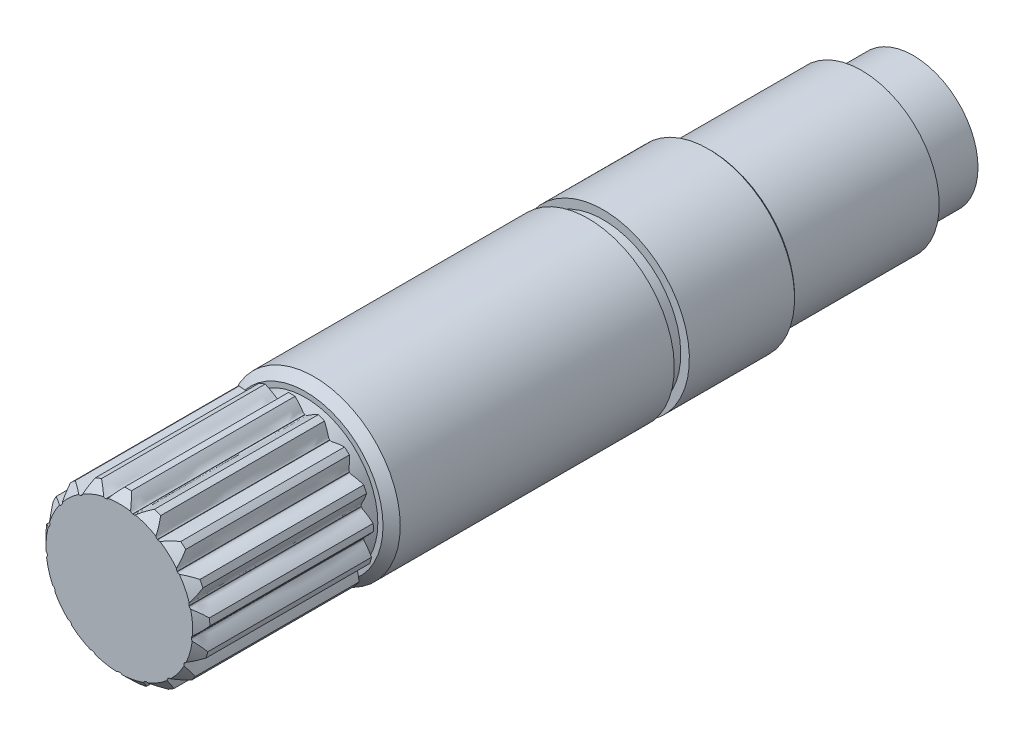
SolidWorks part; units mm, degrees
material "Alloy Steel"
ref_plane "Front Plane" through (0, 0, 0) normal (0, 0, 1) x (1, 0, 0)
ref_plane "Top Plane" through (0, 0, 0) normal (0, 1, 0) x (1, 0, 0)
ref_plane "Right Plane" through (0, 0, 0) normal (1, 0, 0) x (0, 0, -1)
sketch "Sketch12" plane through (0, 0, 0) normal (0, 0, 1) x (1, 0, 0)
  circle A0 centre (0, 0) radius 10
  dimension "D1" = 20
extrude "Shaft" add sketch "Sketch12" along normal mid plane 43
sketch "Sketch13" plane through (0, 0, 21.5) normal (0, 0, 1) x (1, 0, 0)
  circle A0 centre (0, 0) radius 8.3981
  dimension "D1" = 16.7963
extrude "Motor side relief" add sketch "Sketch13" along normal blind 1.587
sketch "Sketch14" plane through (0, 0, -21.5) normal (0, 0, -1) x (-1, 0, 0)
  circle A0 centre (0, 0) radius 8.3981
  dimension "D1" = 16.7963
sketch "Sketch15" plane through (0, 0, 23.087) normal (0, 0, 1) x (1, 0, 0)
  line L38 (4.4402, 7.1283) -> (4.4211, 7.1402)
  line L39 (4.4211, 7.1402) -> (4.4019, 7.1521)
  line L40 (1.5653, 8.251) -> (1.5432, 8.2552)
  line L41 (1.5432, 8.2552) -> (1.521, 8.2593)
  line L42 (-1.521, 8.2593) -> (-1.5432, 8.2552)
  line L43 (-1.5432, 8.2552) -> (-1.5653, 8.251)
  line L44 (-4.4019, 7.1521) -> (-4.4211, 7.1402)
  line L45 (-4.4211, 7.1402) -> (-4.4402, 7.1283)
  line L46 (-6.6882, 5.079) -> (-6.7019, 5.061)
  line L47 (-6.7019, 5.061) -> (-6.7154, 5.043)
  line L48 (-8.0713, 2.32) -> (-8.0776, 2.2983)
  line L49 (-8.0776, 2.2983) -> (-8.0837, 2.2766)
  line L50 (-8.3644, -0.7524) -> (-8.3623, -0.7749)
  line L51 (-8.3623, -0.7749) -> (-8.3602, -0.7973)
  line L52 (-7.5277, -3.7232) -> (-7.5177, -3.7434)
  line L53 (-7.5177, -3.7434) -> (-7.5076, -3.7636)
  line L54 (-5.6744, -6.1911) -> (-5.6578, -6.2063)
  line L55 (-5.6578, -6.2063) -> (-5.6411, -6.2215)
  line L56 (-3.0548, -7.8229) -> (-3.0338, -7.831)
  line L57 (-3.0338, -7.831) -> (-3.0127, -7.8392)
  line L58 (-0.0226, -8.3981) -> (0, -8.3981)
  line L59 (0, -8.3981) -> (0.0226, -8.3981)
  line L60 (3.0127, -7.8392) -> (3.0338, -7.831)
  line L61 (3.0338, -7.831) -> (3.0548, -7.8229)
  line L62 (5.6411, -6.2215) -> (5.6578, -6.2063)
  line L63 (5.6578, -6.2063) -> (5.6744, -6.1911)
  line L64 (7.5076, -3.7636) -> (7.5177, -3.7434)
  line L65 (7.5177, -3.7434) -> (7.5277, -3.7232)
  line L66 (8.3602, -0.7973) -> (8.3623, -0.7749)
  line L67 (8.3623, -0.7749) -> (8.3644, -0.7524)
  line L68 (8.0837, 2.2766) -> (8.0776, 2.2983)
  line L69 (8.0776, 2.2983) -> (8.0713, 2.32)
  line L70 (6.7154, 5.043) -> (6.7019, 5.061)
  line L71 (6.7019, 5.061) -> (6.6882, 5.079)
  arc A19 (6.6912, 6.7683) -> (6.1221, 7.2872) centre (0, 0) ccw
  arc A20 (3.7944, 8.7284) -> (3.0762, 9.0066) centre (0, 0) ccw
  arc A21 (0.3851, 9.5097) -> (-0.3851, 9.5097) centre (0, 0) ccw
  arc A22 (-3.0762, 9.0066) -> (-3.7944, 8.7284) centre (0, 0) ccw
  arc A23 (-6.1221, 7.2872) -> (-6.6912, 6.7683) centre (0, 0) ccw
  arc A24 (-8.3411, 4.5835) -> (-8.6844, 3.8941) centre (0, 0) ccw
  arc A25 (-9.4336, 1.2609) -> (-9.5047, 0.494) centre (0, 0) ccw
  arc A26 (-9.2521, -2.2321) -> (-9.0413, -2.9728) centre (0, 0) ccw
  arc A27 (-7.821, -5.4236) -> (-7.3569, -6.0382) centre (0, 0) ccw
  arc A28 (-5.3336, -7.8826) -> (-4.6788, -8.288) centre (0, 0) ccw
  arc A29 (-2.1259, -9.277) -> (-1.3689, -9.4185) centre (0, 0) ccw
  arc A30 (1.3689, -9.4185) -> (2.1259, -9.277) centre (0, 0) ccw
  arc A31 (4.6788, -8.288) -> (5.3336, -7.8826) centre (0, 0) ccw
  arc A32 (7.3569, -6.0382) -> (7.821, -5.4236) centre (0, 0) ccw
  arc A33 (9.0413, -2.9728) -> (9.2521, -2.2321) centre (0, 0) ccw
  arc A34 (9.5047, 0.494) -> (9.4336, 1.2609) centre (0, 0) ccw
  arc A35 (8.6844, 3.8941) -> (8.3411, 4.5835) centre (0, 0) ccw
  spline S0 degree 3 poles (6.6882, 5.079) (6.6486, 5.1312) (6.6257, 5.1903) (6.6128, 5.3124) (6.6277, 5.3769) (6.657, 5.5736) (6.6884, 5.8472) (6.7084, 6.2901) (6.7009, 6.6058) (6.6912, 6.7683) knots 0 0 0 0 0.125 0.125 0.25 0.25 0.5 0.75 1 1 1 1 weights 1 1 1 1 1 1 1 1 1 1
  spline S1 degree 3 poles (6.1221, 7.2872) (5.9593, 7.2818) (5.6443, 7.2602) (5.2052, 7.1994) (4.9356, 7.1428) (4.7425, 7.0956) (4.6796, 7.0748) (4.5569, 7.0763) (4.4958, 7.0937) (4.4402, 7.1283) knots 0 0 0 0 0.25 0.5 0.75 0.75 0.875 0.875 1 1 1 1 weights 1 1 1 1 1 1 1 1 1 1
  spline S2 degree 3 poles (4.4019, 7.1521) (4.3461, 7.1864) (4.3033, 7.2333) (4.2472, 7.3425) (4.2378, 7.4081) (4.194, 7.602) (4.1245, 7.8685) (3.9832, 8.2887) (3.8621, 8.5804) (3.7944, 8.7284) knots 0 0 0 0 0.125 0.125 0.25 0.25 0.5 0.75 1 1 1 1 weights 1 1 1 1 1 1 1 1 1 1
  spline S3 degree 3 poles (3.0762, 9.0066) (2.9264, 8.9428) (2.6405, 8.8089) (2.253, 8.5935) (2.022, 8.4434) (1.859, 8.3296) (1.8079, 8.2875) (1.6929, 8.2446) (1.6297, 8.2388) (1.5653, 8.251) knots 0 0 0 0 0.25 0.5 0.75 0.75 0.875 0.875 1 1 1 1 weights 1 1 1 1 1 1 1 1 1 1
  spline S4 degree 3 poles (1.521, 8.2593) (1.4566, 8.2711) (1.3997, 8.2994) (1.308, 8.3809) (1.2755, 8.4387) (1.1646, 8.6037) (1.0035, 8.8271) (0.7199, 9.1679) (0.5017, 9.3961) (0.3851, 9.5097) knots 0 0 0 0 0.125 0.125 0.25 0.25 0.5 0.75 1 1 1 1 weights 1 1 1 1 1 1 1 1 1 1
  spline S5 degree 3 poles (-0.3851, 9.5097) (-0.5017, 9.3961) (-0.7199, 9.1679) (-1.0035, 8.8271) (-1.1646, 8.6037) (-1.2755, 8.4387) (-1.308, 8.3809) (-1.3997, 8.2994) (-1.4566, 8.2711) (-1.521, 8.2593) knots 0 0 0 0 0.25 0.5 0.75 0.75 0.875 0.875 1 1 1 1 weights 1 1 1 1 1 1 1 1 1 1
  spline S6 degree 3 poles (-1.5653, 8.251) (-1.6297, 8.2388) (-1.6929, 8.2446) (-1.8079, 8.2875) (-1.859, 8.3296) (-2.022, 8.4434) (-2.253, 8.5935) (-2.6405, 8.8089) (-2.9264, 8.9428) (-3.0762, 9.0066) knots 0 0 0 0 0.125 0.125 0.25 0.25 0.5 0.75 1 1 1 1 weights 1 1 1 1 1 1 1 1 1 1
  spline S7 degree 3 poles (-3.7944, 8.7284) (-3.8621, 8.5804) (-3.9832, 8.2887) (-4.1245, 7.8685) (-4.194, 7.602) (-4.2378, 7.4081) (-4.2472, 7.3425) (-4.3033, 7.2333) (-4.3461, 7.1864) (-4.4019, 7.1521) knots 0 0 0 0 0.25 0.5 0.75 0.75 0.875 0.875 1 1 1 1 weights 1 1 1 1 1 1 1 1 1 1
  spline S8 degree 3 poles (-4.4402, 7.1283) (-4.4958, 7.0937) (-4.5569, 7.0763) (-4.6796, 7.0748) (-4.7425, 7.0956) (-4.9356, 7.1428) (-5.2052, 7.1994) (-5.6443, 7.2602) (-5.9593, 7.2818) (-6.1221, 7.2872) knots 0 0 0 0 0.125 0.125 0.25 0.25 0.5 0.75 1 1 1 1 weights 1 1 1 1 1 1 1 1 1 1
  spline S9 degree 3 poles (-6.6912, 6.7683) (-6.7009, 6.6058) (-6.7084, 6.2901) (-6.6884, 5.8472) (-6.657, 5.5736) (-6.6277, 5.3769) (-6.6128, 5.3124) (-6.6257, 5.1903) (-6.6486, 5.1312) (-6.6882, 5.079) knots 0 0 0 0 0.25 0.5 0.75 0.75 0.875 0.875 1 1 1 1 weights 1 1 1 1 1 1 1 1 1 1
  spline S10 degree 3 poles (-6.7154, 5.043) (-6.7548, 4.9906) (-6.8054, 4.9523) (-6.9193, 4.9066) (-6.9854, 4.9033) (-7.1826, 4.8775) (-7.4544, 4.8329) (-7.8859, 4.7309) (-8.1874, 4.6373) (-8.3411, 4.5835) knots 0 0 0 0 0.125 0.125 0.25 0.25 0.5 0.75 1 1 1 1 weights 1 1 1 1 1 1 1 1 1 1
  spline S11 degree 3 poles (-8.6844, 3.8941) (-8.6347, 3.7391) (-8.5277, 3.442) (-8.349, 3.0363) (-8.2209, 2.7925) (-8.1225, 2.6196) (-8.0853, 2.5648) (-8.0532, 2.4464) (-8.0533, 2.3829) (-8.0713, 2.32) knots 0 0 0 0 0.25 0.5 0.75 0.75 0.875 0.875 1 1 1 1 weights 1 1 1 1 1 1 1 1 1 1
  spline S12 degree 3 poles (-8.0837, 2.2766) (-8.1015, 2.2135) (-8.1348, 2.1595) (-8.2245, 2.0757) (-8.285, 2.0487) (-8.4596, 1.9535) (-8.6968, 1.8137) (-9.0624, 1.5628) (-9.3097, 1.3665) (-9.4336, 1.2609) knots 0 0 0 0 0.125 0.125 0.25 0.25 0.5 0.75 1 1 1 1 weights 1 1 1 1 1 1 1 1 1 1
  spline S13 degree 3 poles (-9.5047, 0.494) (-9.4023, 0.3674) (-9.1952, 0.129) (-8.882, -0.1848) (-8.6745, -0.3658) (-8.5204, -0.4915) (-8.4659, -0.5291) (-8.3931, -0.628) (-8.3702, -0.6872) (-8.3644, -0.7524) knots 0 0 0 0 0.25 0.5 0.75 0.75 0.875 0.875 1 1 1 1 weights 1 1 1 1 1 1 1 1 1 1
  spline S14 degree 3 poles (-8.3602, -0.7973) (-8.354, -0.8625) (-8.3656, -0.925) (-8.419, -1.0355) (-8.4656, -1.0825) (-8.594, -1.2344) (-8.7647, -1.4504) (-9.0149, -1.8164) (-9.1747, -2.0888) (-9.2521, -2.2321) knots 0 0 0 0 0.125 0.125 0.25 0.25 0.5 0.75 1 1 1 1 weights 1 1 1 1 1 1 1 1 1 1
  spline S15 degree 3 poles (-9.0413, -2.9728) (-8.9001, -3.0539) (-8.6209, -3.2014) (-8.2155, -3.3809) (-7.9566, -3.4747) (-7.7675, -3.5362) (-7.7031, -3.5516) (-7.5995, -3.6175) (-7.5568, -3.6645) (-7.5277, -3.7232) knots 0 0 0 0 0.25 0.5 0.75 0.75 0.875 0.875 1 1 1 1 weights 1 1 1 1 1 1 1 1 1 1
  spline S16 degree 3 poles (-7.5076, -3.7636) (-7.4783, -3.8221) (-7.4666, -3.8845) (-7.4764, -4.0068) (-7.5029, -4.0675) (-7.5678, -4.2555) (-7.6489, -4.5187) (-7.75, -4.9504) (-7.8006, -5.262) (-7.821, -5.4236) knots 0 0 0 0 0.125 0.125 0.25 0.25 0.5 0.75 1 1 1 1 weights 1 1 1 1 1 1 1 1 1 1
  spline S17 degree 3 poles (-7.3569, -6.0382) (-7.1959, -6.0628) (-6.8823, -6.0994) (-6.4394, -6.1203) (-6.1641, -6.1143) (-5.9655, -6.1033) (-5.8999, -6.0945) (-5.7795, -6.1185) (-5.7227, -6.1468) (-5.6744, -6.1911) knots 0 0 0 0 0.25 0.5 0.75 0.75 0.875 0.875 1 1 1 1 weights 1 1 1 1 1 1 1 1 1 1
  spline S18 degree 3 poles (-5.6411, -6.2215) (-5.5926, -6.2655) (-5.5591, -6.3194) (-5.5241, -6.437) (-5.5269, -6.5032) (-5.5195, -6.7019) (-5.5001, -6.9766) (-5.4384, -7.4157) (-5.373, -7.7246) (-5.3336, -7.8826) knots 0 0 0 0 0.125 0.125 0.25 0.25 0.5 0.75 1 1 1 1 weights 1 1 1 1 1 1 1 1 1 1
  spline S19 degree 3 poles (-4.6788, -8.288) (-4.5198, -8.2528) (-4.2142, -8.1737) (-3.7936, -8.0332) (-3.5391, -7.9281) (-3.3579, -7.8462) (-3.2999, -7.8142) (-3.179, -7.7931) (-3.1158, -7.799) (-3.0548, -7.8229) knots 0 0 0 0 0.25 0.5 0.75 0.75 0.875 0.875 1 1 1 1 weights 1 1 1 1 1 1 1 1 1 1
  spline S20 degree 3 poles (-3.0127, -7.8392) (-2.9516, -7.8627) (-2.9009, -7.9009) (-2.8257, -7.9979) (-2.8044, -8.0606) (-2.7257, -8.2432) (-2.6084, -8.4924) (-2.3923, -8.8795) (-2.2197, -9.1439) (-2.1259, -9.277) knots 0 0 0 0 0.125 0.125 0.25 0.25 0.5 0.75 1 1 1 1 weights 1 1 1 1 1 1 1 1 1 1
  spline S21 degree 3 poles (-1.3689, -9.4185) (-1.2333, -9.3283) (-0.9769, -9.1441) (-0.6355, -8.8612) (-0.4361, -8.6712) (-0.2968, -8.5294) (-0.2543, -8.4786) (-0.1491, -8.4153) (-0.0881, -8.3979) (-0.0226, -8.3981) knots 0 0 0 0 0.25 0.5 0.75 0.75 0.875 0.875 1 1 1 1 weights 1 1 1 1 1 1 1 1 1 1
  spline S22 degree 3 poles (0.0226, -8.3981) (0.0881, -8.3979) (0.1491, -8.4153) (0.2543, -8.4786) (0.2968, -8.5294) (0.4361, -8.6712) (0.6355, -8.8612) (0.9769, -9.1441) (1.2333, -9.3283) (1.3689, -9.4185) knots 0 0 0 0 0.125 0.125 0.25 0.25 0.5 0.75 1 1 1 1 weights 1 1 1 1 1 1 1 1 1 1
  spline S23 degree 3 poles (2.1259, -9.277) (2.2197, -9.1439) (2.3923, -8.8795) (2.6084, -8.4924) (2.7257, -8.2432) (2.8044, -8.0606) (2.8257, -7.9979) (2.9009, -7.9009) (2.9516, -7.8627) (3.0127, -7.8392) knots 0 0 0 0 0.25 0.5 0.75 0.75 0.875 0.875 1 1 1 1 weights 1 1 1 1 1 1 1 1 1 1
  spline S24 degree 3 poles (3.0548, -7.8229) (3.1158, -7.799) (3.179, -7.7931) (3.2999, -7.8142) (3.3579, -7.8462) (3.5391, -7.9281) (3.7936, -8.0332) (4.2142, -8.1737) (4.5198, -8.2528) (4.6788, -8.288) knots 0 0 0 0 0.125 0.125 0.25 0.25 0.5 0.75 1 1 1 1 weights 1 1 1 1 1 1 1 1 1 1
  spline S25 degree 3 poles (5.3336, -7.8826) (5.373, -7.7246) (5.4384, -7.4157) (5.5001, -6.9766) (5.5195, -6.7019) (5.5269, -6.5032) (5.5241, -6.437) (5.5591, -6.3194) (5.5926, -6.2655) (5.6411, -6.2215) knots 0 0 0 0 0.25 0.5 0.75 0.75 0.875 0.875 1 1 1 1 weights 1 1 1 1 1 1 1 1 1 1
  spline S26 degree 3 poles (5.6744, -6.1911) (5.7227, -6.1468) (5.7795, -6.1185) (5.8999, -6.0945) (5.9655, -6.1033) (6.1641, -6.1143) (6.4394, -6.1203) (6.8823, -6.0994) (7.1959, -6.0628) (7.3569, -6.0382) knots 0 0 0 0 0.125 0.125 0.25 0.25 0.5 0.75 1 1 1 1 weights 1 1 1 1 1 1 1 1 1 1
  spline S27 degree 3 poles (7.821, -5.4236) (7.8006, -5.262) (7.75, -4.9504) (7.6489, -4.5187) (7.5678, -4.2555) (7.5029, -4.0675) (7.4764, -4.0068) (7.4666, -3.8845) (7.4783, -3.8221) (7.5076, -3.7636) knots 0 0 0 0 0.25 0.5 0.75 0.75 0.875 0.875 1 1 1 1 weights 1 1 1 1 1 1 1 1 1 1
  spline S28 degree 3 poles (7.5277, -3.7232) (7.5568, -3.6645) (7.5995, -3.6175) (7.7031, -3.5516) (7.7675, -3.5362) (7.9566, -3.4747) (8.2155, -3.3809) (8.6209, -3.2014) (8.9001, -3.0539) (9.0413, -2.9728) knots 0 0 0 0 0.125 0.125 0.25 0.25 0.5 0.75 1 1 1 1 weights 1 1 1 1 1 1 1 1 1 1
  spline S29 degree 3 poles (9.2521, -2.2321) (9.1747, -2.0888) (9.0149, -1.8164) (8.7647, -1.4504) (8.594, -1.2344) (8.4656, -1.0825) (8.419, -1.0355) (8.3656, -0.925) (8.354, -0.8625) (8.3602, -0.7973) knots 0 0 0 0 0.25 0.5 0.75 0.75 0.875 0.875 1 1 1 1 weights 1 1 1 1 1 1 1 1 1 1
  spline S30 degree 3 poles (8.3644, -0.7524) (8.3702, -0.6872) (8.3931, -0.628) (8.4659, -0.5291) (8.5204, -0.4915) (8.6745, -0.3658) (8.882, -0.1848) (9.1952, 0.129) (9.4023, 0.3674) (9.5047, 0.494) knots 0 0 0 0 0.125 0.125 0.25 0.25 0.5 0.75 1 1 1 1 weights 1 1 1 1 1 1 1 1 1 1
  spline S31 degree 3 poles (9.4336, 1.2609) (9.3097, 1.3665) (9.0624, 1.5628) (8.6968, 1.8137) (8.4596, 1.9535) (8.285, 2.0487) (8.2245, 2.0757) (8.1348, 2.1595) (8.1015, 2.2135) (8.0837, 2.2766) knots 0 0 0 0 0.25 0.5 0.75 0.75 0.875 0.875 1 1 1 1 weights 1 1 1 1 1 1 1 1 1 1
  spline S32 degree 3 poles (8.0713, 2.32) (8.0533, 2.3829) (8.0532, 2.4464) (8.0853, 2.5648) (8.1225, 2.6196) (8.2209, 2.7925) (8.349, 3.0363) (8.5277, 3.442) (8.6347, 3.7391) (8.6844, 3.8941) knots 0 0 0 0 0.125 0.125 0.25 0.25 0.5 0.75 1 1 1 1 weights 1 1 1 1 1 1 1 1 1 1
  spline S33 degree 3 poles (8.3411, 4.5835) (8.1874, 4.6373) (7.8858, 4.731) (7.4544, 4.8329) (7.1826, 4.8775) (6.9854, 4.9033) (6.9193, 4.9066) (6.8054, 4.9523) (6.7548, 4.9906) (6.7154, 5.043) knots 0 0 0 0 0.25 0.5 0.75 0.75 0.875 0.875 1 1 1 1 weights 1 1 1 1 1 1 1 1 1 1
extrude "Motor spline" add sketch "Sketch15" along normal blind 20
chamfer "Chamfer3" distance 1 angle 45 1 edges at (10, 0, 21.5)
sketch "Sketch23" plane through (0, 0, -31.5) normal (-0.948, 0.3182, 0) x (-0.3182, -0.948, 0)
  line L0 (10, 20.2042) -> (9, 20.2042)
  line L1 (9, 20.2042) -> (9, 18.4542)
  line L2 (9, 18.4542) -> (10, 18.4542)
  line L3 (10, 18.4542) -> (10, 20.2042)
  line L4 (10, 10) -> (10, 52) construction
  line L5 (-13.85, 20.2042) -> (13.85, 20.2042) construction
  line L7 (0, 185.3358) -> (0, -121.609) construction
  dimension "D1" = 1.75
  dimension "D2" = 1
revolve "snap ring" cut sketch "Sketch23" angle 360 about L7
sketch "Sketch24" plane through (0, 0, 0) normal (0, 1, 0) x (1, 0, 0)
  line L3 (10, 21.5) -> (10, 25.5)
  line L5 (7.5, 43.5) -> (7.5, 49.5)
  line L6 (7.5, 49.5) -> (0, 49.5)
  line L7 (0, 49.5) -> (0, 21.5)
  line L8 (10, 21.5) -> (-10, 21.5) construction
  line L9 (0, 21.5) -> (10, 21.5)
  line L10 (0, 0) -> (0, 49.7252) construction
  line L12 (7.5, 43.5) -> (9, 43.5)
  line L14 (10, 25.5) -> (9, 25.5)
  line L15 (9, 25.5) -> (9, 43.5)
  dimension "D1" = 15
  dimension "D2" = 22
  dimension "D3" = 4
  dimension "D8" = 6
revolve "Revolve1" add sketch "Sketch24" angle 360 about L10
chamfer "Chamfer4" distance 1 angle 25 2 edges at (9, 0, -43.5) (7.5, 0, -49.5) first distance on face at (7.5, 0, -43.5) first distance on face at (7.5, 0, -49.5)
chamfer "Chamfer5" distance 0.25 angle 45 1 edges at (10, 0, -25.5)
chamfer "Chamfer6" distance 1 angle 45 17 edges
